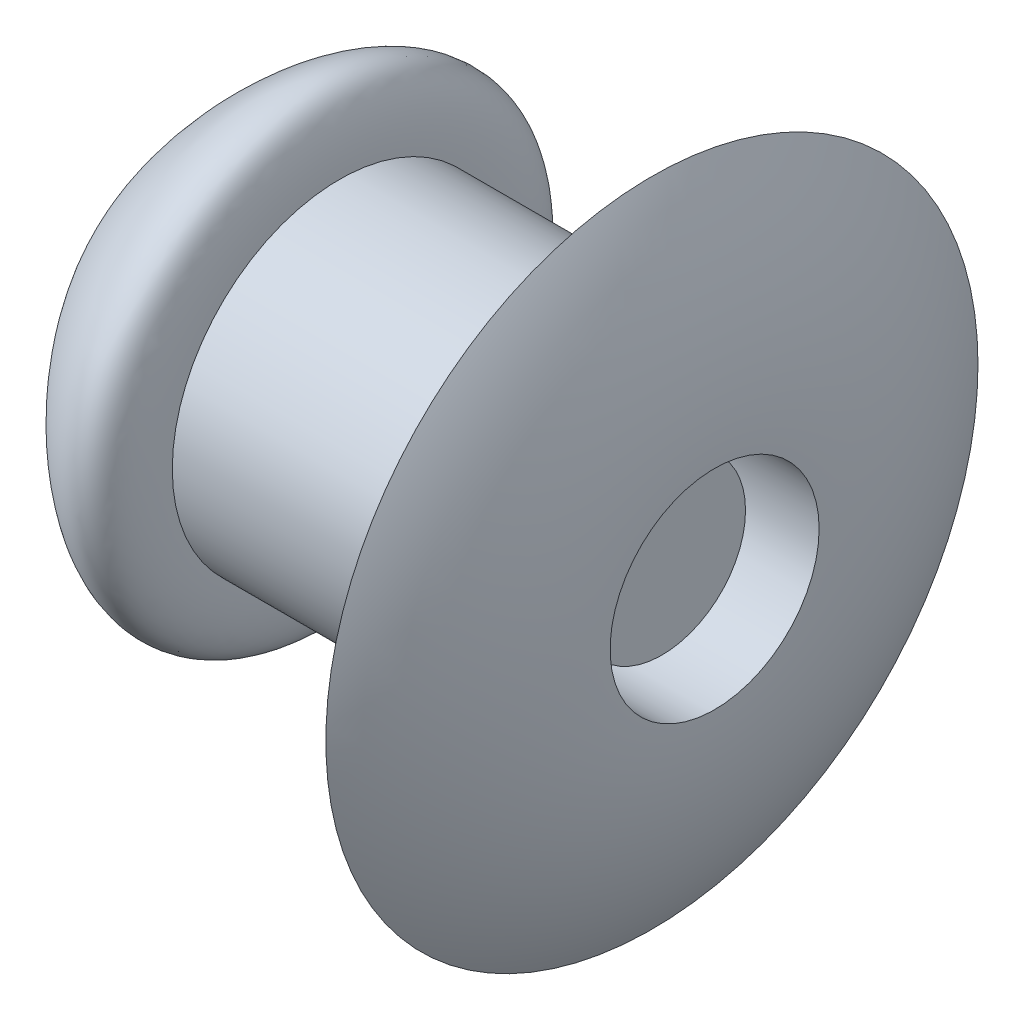
SolidWorks part; units mm, degrees
material "AISI 316 Arkusz stali nierdzewnej (SS)"
ref_plane "Płaszczyzna przednia" through (0, 0, 0) normal (0, 0, 1) x (1, 0, 0)
ref_plane "Płaszczyzna górna" through (0, 0, 0) normal (0, 1, 0) x (1, 0, 0)
ref_plane "Płaszczyzna prawa" through (0, 0, 0) normal (1, 0, 0) x (0, 0, -1)
sketch "Szkic1" plane through (0, 0, 0) normal (0, 0, 1) x (1, 0, 0)
  line L0 (350.8561, 893.6816) -> (345.4445, 893.6816)
  line L1 (351.4866, 894.9316) -> (347, 894.9316)
  line L2 (347, 894.9316) -> (347, 894.6816)
  line L3 (347, 894.6816) -> (350.8561, 894.6816)
  line L4 (350.8561, 894.6816) -> (350.8561, 893.6816)
  line L5 (350.7366, 897.5816) -> (350.7366, 895.6816)
  line L6 (350.7366, 895.6816) -> (347, 895.6816)
  line L7 (350.8561, 893.6816) -> (345.4445, 893.6816) construction
  line L8 (350.8561, 893.6816) -> (345.4445, 893.6816) construction
  line L9 (351.4866, 893.6816) -> (350.8561, 893.6816) construction
  line L10 (350.7366, 521.1816) -> (350.7366, 901.1816) construction
  line L11 (347, 4.3583) -> (347, 898.0048) construction
  arc A0 (351.4866, 894.9316) -> (350.7366, 897.5816) centre (346.4299, 894.9316) ccw
  spline S0 degree 3 poles (347, 895.6816) (347.0366, 898.0214) (343.5366, 893.3094) (345.7587, 895.1701) (346.0554, 894.8565) knots 0 0 0 0 0.744502 1 1 1 1
  spline S1 degree 2 poles (346.0554, 894.8565) (345.1724, 894.8746) (345.4445, 893.6816) knots 0 0 0 1 1 1
  dimension "D18" = 4.8231
  dimension "D1" = 2
  dimension "D2" = 0.1195
  dimension "D3" = 4
  dimension "D4" = 2.5
  dimension "D5" = 0.75
  dimension "D6" = 7.8
  dimension "D7" = 0.9668
  dimension "D8" = 1.1117
  dimension "D9" = 1.175
  dimension "D10" = 1.2811
  dimension "D11" = 2.7999
  dimension "D12" = 0.4548
  dimension "D13" = 0.9446
  dimension "D14" = 1.1893
  dimension "D15" = 1.3067
  dimension "D16" = 2.0033
  dimension "D17" = 1.5555
revolve "Obrót1" add sketch "Szkic1" angle 360 about L7
